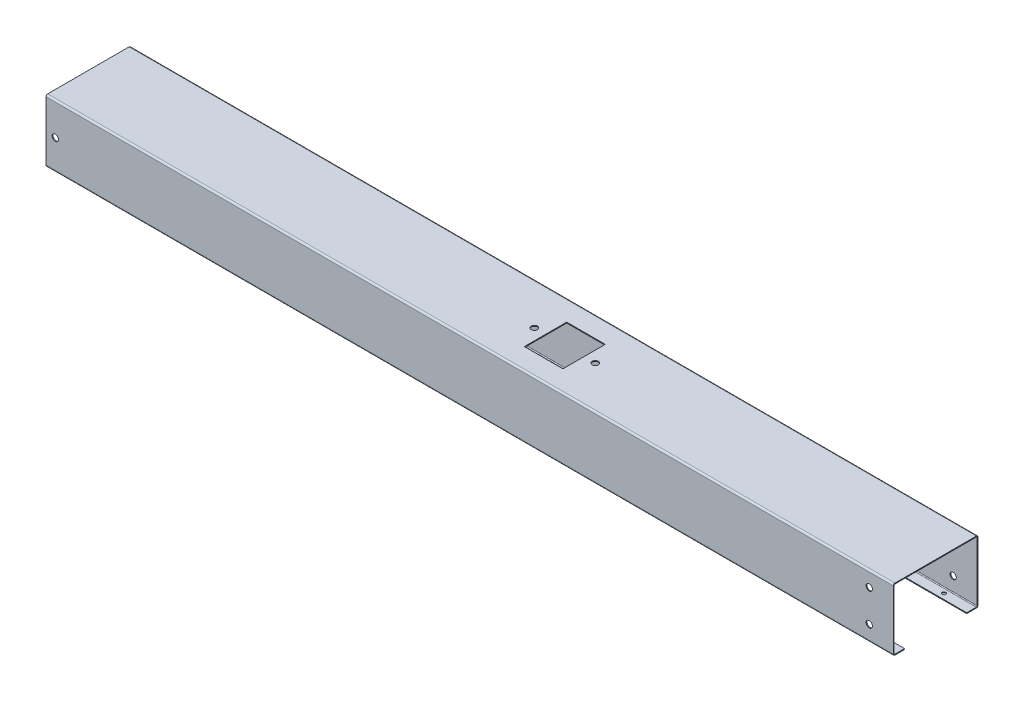
SolidWorks part; units mm, degrees
note: The reader was unsure of these and kept them because the rebuilt part matched: thickness of "Base-Flange1", "Edge-Flange1", "Edge-Flange2", "Sheet-Metal1", "Sheet-Metal2", "Sheet-Metal3", "Sheet-Metal5", "Sheet-Metal15", "Sheet-Metal16", "Sheet-Metal17", "Sheet-Metal18", "Sheet-Metal19"; flange length of "Edge-Flange1", "Edge-Flange2".
ref_plane "Front Plane" through (0, 0, 0) normal (0, 0, 1) x (1, 0, 0)
ref_plane "Top Plane" through (0, 0, 0) normal (0, 1, 0) x (1, 0, 0)
ref_plane "Right Plane" through (0, 0, 0) normal (1, 0, 0) x (0, 0, -1)
sketch "Sketch1" plane through (0, 0, 0) normal (0, 1, 0) x (1, 0, 0)
  line L1 (-381, -38.1) -> (381, -38.1)
  line L2 (-381, -38.1) -> (-381, 38.1)
  line L3 (-381, 38.1) -> (381, 38.1)
  line L4 (381, -38.1) -> (381, 38.1)
  line L5 (-381, -38.1) -> (381, 38.1) construction
  line L6 (-381, 38.1) -> (381, -38.1) construction
  point P0 (0, 0)
  dimension "D1" = 762
  dimension "D2" = 76.2
base flange "Base-Flange1" sketch "Sketch1" thickness 0.7595 reverse thickness direction no parameters "D1"=0.7366
sketch "Sketch6" plane through (0, 0, 0) normal (0, 1, 0) x (1, 0, 0)
  line L0 (53.7835, 19.05) -> (64.8335, 19.05)
  line L1 (30.1625, -19.05) -> (53.7835, -19.05)
  line L2 (30.1625, -19.05) -> (30.1625, 19.05)
  line L3 (30.1625, 19.05) -> (53.7835, 19.05)
  line L4 (64.8335, -19.05) -> (64.8335, 19.05)
  line L5 (30.1625, -19.05) -> (64.8335, 19.05) construction
  line L6 (30.1625, 19.05) -> (64.8335, -19.05) construction
  line L11 (-381, -38.1) -> (381, -38.1) construction
  line L12 (-381, 38.1) -> (-381, -38.1) construction
  line L13 (53.7835, -19.05) -> (64.8335, -19.05)
  point P0 (47.498, 0)
  point P12 (30.1625, 0)
  point P16 (64.8335, 0)
  dimension "D1" = 34.671
  dimension "D2" = 38.1
  dimension "D3" = 38.1
  dimension "D4" = 428.498
extrude "Cut-Extrude1" cut sketch "Sketch6" against normal blind 10 normal cut yes
sketch "Sketch7" plane through (0, 0, 0) normal (0, 1, 0) x (1, 0, 0)
  line L0 (30.1625, 19.05) -> (30.1625, -19.05) construction
  line L1 (64.8335, -19.05) -> (64.8335, 19.05) construction
  circle A0 centre (20.0625, 0) radius 2.8194
  circle A1 centre (74.9335, 0) radius 2.8194
  dimension "D1" = 5.6388
  dimension "D2" = 10.1
  dimension "D4" = 5.6388
  dimension "D3" = 10.1
extrude "Cut-Extrude2" cut sketch "Sketch7" against normal blind 10 normal cut yes
edge flange "Edge-Flange1" sketch "Sketch37" flange profiles "Sketch37", "Sketch39" flange angle 90 flange length 55.372 flange position material inside bend radius 0.7366 thickness 0.7595 relief rectangular parameters "D6"=10, "D8"=0.254
sketch "Sketch37" plane through (0, -0.7595, -38.1) normal (0, 0, -1) x (1, 0, 0)
  line L0 (381, 0) -> (-381, 0) construction
  line L1 (381, 0) -> (-381, 0)
  line L2 (-381, 0) -> (-381, 54.6125)
  line L3 (-381, 54.6125) -> (381, 54.6125)
  line L4 (381, 54.6125) -> (381, 0)
sketch "Sketch39" plane through (0, -0.7595, 38.1) normal (0, 0, 1) x (-1, 0, 0)
  line L0 (381, 0) -> (-381, 0) construction
  line L1 (381, 0) -> (-381, 0)
  line L2 (-381, 0) -> (-381, 54.6125)
  line L3 (-381, 54.6125) -> (381, 54.6125)
  line L4 (381, 54.6125) -> (381, 0)
bend "EdgeBend8" bend radius 0.7366 bend angle 90 parameters "D5"=4
bend "EdgeBend9" bend radius 0.7366 bend angle 90 parameters "D5"=5
sketch "Sketch41" plane through (0, 0, -38.1) normal (0, 0, -1) x (-1, 0, 0)
  line L0 (365.66, -13.4595) -> (352.96, -13.4595) construction
  line L1 (365.66, -16.825) -> (352.96, -16.825)
  line L2 (365.66, -10.094) -> (352.96, -10.094)
  line L3 (381, -55.372) -> (381, -1.4961) construction
  line L6 (-353.06, -13.448) -> (-365.76, -13.448) construction
  line L7 (-353.06, -16.8135) -> (-365.76, -16.8135)
  line L10 (-353.06, -10.0825) -> (-365.76, -10.0825)
  line L11 (-381, 0) -> (-381, -1.4961) construction
  line L12 (-381, -1.4961) -> (-381, -55.372) construction
  arc A0 (365.66, -16.825) -> (365.66, -10.094) centre (365.66, -13.4595) ccw
  arc A1 (352.96, -10.094) -> (352.96, -16.825) centre (352.96, -13.4595) ccw
  arc A4 (-353.06, -16.8135) -> (-353.06, -10.0825) centre (-353.06, -13.448) ccw
  arc A5 (-365.76, -10.0825) -> (-365.76, -16.8135) centre (-365.76, -13.448) ccw
  point P2 (359.31, -13.4595)
  point P11 (-359.41, -13.448)
  point P21 (-381, -0.748)
  dimension "D1" = 6.731
  dimension "D4" = 12.7
  dimension "D8" = 6.731
  dimension "D2" = 21.69
  dimension "D3" = 12.7
  dimension "D5" = 12.7
  dimension "D6" = 21.59
  dimension "D7" = 12.7
extrude "Cut-Extrude3" [suppressed] cut sketch "Sketch41" against normal through all both and the other way through all
sketch "Sketch42" plane through (0, 0, -38.1) normal (0, 0, -1) x (-1, 0, 0)
  line L0 (-381, -55.372) -> (381, -55.372) construction
  line L1 (-381, -1.4961) -> (-381, -55.372) construction
  circle A0 centre (-359.41, -13.4595) radius 2.8194
  circle A1 centre (-359.41, -42.164) radius 2.8194
  dimension "D3" = 5.6388
  dimension "D1" = 12.7
  dimension "D2" = 21.59
  dimension "D4" = 21.59
  dimension "D5" = 13.208
extrude "Cut-Extrude4" cut sketch "Sketch42" against normal through all both and the other way through all normal cut yes
edge flange "Edge-Flange2" sketch "Sketch47" flange profiles "Sketch47", "Sketch48" flange angle 90 flange length 10.16 flange position material outside bend radius 0.7366 thickness 0.7595 relief rectangular parameters "D6"=10, "D8"=0.254
sketch "Sketch47" plane through (0, -55.372, -37.3405) normal (0, 1, 0) x (-1, 0, 0)
  line L2 (-381, 0) -> (-381, 9.4005)
  line L3 (-381, 9.4005) -> (381, 9.4005)
  line L4 (381, 9.4005) -> (381, 0)
  line L5 (381, 0) -> (-381, 0) construction
  line L6 (381, 0) -> (-381, 0)
sketch "Sketch48" plane through (0, -55.372, 37.3405) normal (0, 1, 0) x (1, 0, 0)
  line L0 (381, 0) -> (-381, 0) construction
  line L1 (381, 0) -> (-381, 0)
  line L2 (381, 0) -> (381, 9.4005)
  line L3 (381, 9.4005) -> (-381, 9.4005)
  line L4 (-381, 9.4005) -> (-381, 0)
bend "EdgeBend10" bend radius 0.7366 bend angle 90 parameters "D5"=6
bend "EdgeBend11" bend radius 0.7366 bend angle 90 parameters "D5"=7
sketch "Sketch49" plane through (0, -56.1315, 0) normal (0, -1, 0) x (1, 0, 0)
  line L0 (-381, 36.6039) -> (381, 36.6039) construction
  line L1 (381, 36.6039) -> (381, 27.94) construction
  circle A0 centre (254, -32.7939) radius 1.651
  circle A1 centre (254, 32.7939) radius 1.651
  circle A2 centre (0, 32.7939) radius 1.651
  circle A3 centre (0, -32.7939) radius 1.651
  circle A4 centre (-304.8, -32.7939) radius 1.651
  circle A5 centre (-304.8, 32.7939) radius 1.651
  circle A6 centre (-355.6, 32.7939) radius 1.651
  circle A7 centre (-355.6, -32.7939) radius 1.651
  circle A8 centre (355.6, -32.7939) radius 1.651
  circle A9 centre (355.6, 32.7939) radius 1.651
  circle A10 centre (152.4, 32.7939) radius 1.651
  circle A11 centre (152.4, -32.7939) radius 1.651
  circle A12 centre (-152.4, 32.7939) radius 1.651
  circle A13 centre (-152.4, -32.7939) radius 1.651
  dimension "D1" = 3.302
  dimension "D2" = 3.81
  dimension "D3" = 3.81
  dimension "D4" = 127
  dimension "D5" = 254
  dimension "D6" = 304.8
  dimension "D7" = 50.8
  dimension "D8" = 152.4
  dimension "D9" = 101.6
  dimension "D10" = 101.6
extrude "Cut-Extrude5" cut sketch "Sketch49" against normal up to next normal cut yes
sketch "Sketch50" plane through (0, 0, 38.1) normal (0, 0, 1) x (1, 0, 0)
  line L0 (-381, -1.4961) -> (-381, -54.6354) construction
  circle A0 centre (-372.618, -29.21) radius 2.8194
  dimension "D1" = 5.6388
  dimension "D2" = 29.21
  dimension "D3" = 8.382
extrude "Cut-Extrude6" cut sketch "Sketch50" against normal through all both and the other way through all normal cut yes
sketch "Bend-Lines1" [suppressed] plane through (0, 0, 0) normal (0, 1, 0) x (1, 0, 0)
sketch "Bounding-Box1" [suppressed] plane through (0, 0, 0) normal (0, 1, 0) x (1, 0, 0)
sheet metal parameters "Sheet-Metal1" thickness 0.7595 parameters "D1"=0.7366
flat pattern "Flat-Pattern1" [suppressed]
sketch "Bend-Lines2" plane through (0, 0, 0) normal (0, 1, 0) x (1, 0, 0)
sketch3d "Bounding-Box2" [suppressed]
  line L0 (50.8, 38.1, 0) -> (-50.8, 38.1, 0) construction
  line L1 (50.8, -38.1, 0) -> (-50.8, -38.1, 0) construction
  line L2 (50.8, 38.1, 0) -> (50.8, -38.1, 0) construction
  line L3 (-50.8, 38.1, 0) -> (-50.8, -38.1, 0) construction
sheet metal parameters "Sheet-Metal2" thickness 0.7595 parameters "D1"=0.7366, "D7"=1.7366
flat pattern "Flat-Pattern1"
sketch "Bend-Lines2" plane through (0, 0, 0) normal (0, 1, 0) x (1, 0, 0)
sketch3d "Bounding-Box2" [suppressed]
  line L0 (571.5, 38.1, 0) -> (-571.5, 38.1, 0) construction
  line L1 (571.5, -38.1, 0) -> (-571.5, -38.1, 0) construction
  line L2 (571.5, 38.1, 0) -> (571.5, -38.1, 0) construction
  line L3 (-571.5, 38.1, 0) -> (-571.5, -38.1, 0) construction
sheet metal parameters "Sheet-Metal3" thickness 0.7595 parameters "D1"=0.7366, "D7"=1.7366
flat pattern "Flat-Pattern1"
sketch "Bend-Lines2" plane through (0, 0, 0) normal (0, 1, 0) x (1, 0, 0)
sketch3d "Bounding-Box2" [suppressed]
  line L0 (571.5, 31.75, 0) -> (-571.5, 31.75, 0) construction
  line L1 (571.5, -31.75, 0) -> (-571.5, -31.75, 0) construction
  line L2 (571.5, 31.75, 0) -> (571.5, -31.75, 0) construction
  line L3 (-571.5, 31.75, 0) -> (-571.5, -31.75, 0) construction
sheet metal parameters "Sheet-Metal5" thickness 0.7595 parameters "D1"=0.7366, "D7"=1.7366
flat pattern "Flat-Pattern1"
sketch "Bend-Lines2" plane through (0, 0, 0) normal (0, 1, 0) x (1, 0, 0)
  line L2 (-381, -37.4807) -> (381, -37.4807) construction
  line L3 (381, 37.4807) -> (-381, 37.4807) construction
  line L5 (-381, -37.4807) -> (381, -37.4807) construction
  line L6 (381, 37.4807) -> (-381, 37.4807) construction
sketch3d "Bounding-Box2" [suppressed]
  line L0 (381, 94.0114, 0) -> (-381, 94.0114, 0) construction
  line L1 (381, -94.0114, 0) -> (-381, -94.0114, 0) construction
  line L2 (381, 94.0114, 0) -> (381, -94.0114, 0) construction
  line L3 (-381, 94.0114, 0) -> (-381, -94.0114, 0) construction
bend of the flat pattern "Flatten-<EdgeBend8>1"
bend of the flat pattern "Flatten-<EdgeBend9>1"
sheet metal parameters "Sheet-Metal15" thickness 0.7595 parameters "D1"=0.7366, "D7"=1.7366
flat pattern "Flat-Pattern1"
sketch "Bend-Lines2" plane through (0, 0, 0) normal (0, 1, 0) x (1, 0, 0)
  line L2 (-381, -37.4807) -> (381, -37.4807) construction
  line L3 (381, 37.4807) -> (-381, 37.4807) construction
  line L5 (-381, -37.4807) -> (381, -37.4807) construction
  line L6 (381, 37.4807) -> (-381, 37.4807) construction
sketch3d "Bounding-Box2" [suppressed]
  line L0 (381, 94.0114, 0) -> (-381, 94.0114, 0) construction
  line L1 (381, -94.0114, 0) -> (-381, -94.0114, 0) construction
  line L2 (381, 94.0114, 0) -> (381, -94.0114, 0) construction
  line L3 (-381, 94.0114, 0) -> (-381, -94.0114, 0) construction
bend of the flat pattern "Flatten-<EdgeBend8>1"
bend of the flat pattern "Flatten-<EdgeBend9>1"
sheet metal parameters "Sheet-Metal16" thickness 0.7595 parameters "D1"=0.7366, "D7"=1.7366
flat pattern "Flat-Pattern1"
sketch "Bend-Lines2" plane through (0, 0, 0) normal (0, 1, 0) x (1, 0, 0)
  line L2 (-381, -37.4807) -> (381, -37.4807) construction
  line L3 (381, 37.4807) -> (-381, 37.4807) construction
  line L5 (-381, -37.4807) -> (381, -37.4807) construction
  line L6 (381, 37.4807) -> (-381, 37.4807) construction
sketch3d "Bounding-Box2" [suppressed]
  line L0 (381, 93.5034, 0) -> (-381, 93.5034, 0) construction
  line L1 (381, -93.5034, 0) -> (-381, -93.5034, 0) construction
  line L2 (381, 93.5034, 0) -> (381, -93.5034, 0) construction
  line L3 (-381, 93.5034, 0) -> (-381, -93.5034, 0) construction
bend of the flat pattern "Flatten-<EdgeBend8>1"
bend of the flat pattern "Flatten-<EdgeBend9>1"
sheet metal parameters "Sheet-Metal17" thickness 0.7595 parameters "D1"=0.7366, "D7"=1.7366
flat pattern "Flat-Pattern1"
sketch "Bend-Lines2" plane through (0, 0, 0) normal (0, 1, 0) x (1, 0, 0)
  line L0 (-381, -93.6436) -> (381, -93.6436) construction
  line L1 (381, 93.6436) -> (-381, 93.6436) construction
  line L2 (-381, -37.4807) -> (381, -37.4807) construction
  line L3 (381, 37.4807) -> (-381, 37.4807) construction
  line L4 (-381, -93.6436) -> (381, -93.6436) construction
  line L5 (-381, -37.4807) -> (381, -37.4807) construction
  line L6 (381, 37.4807) -> (-381, 37.4807) construction
  line L7 (381, 93.6436) -> (-381, 93.6436) construction
sketch3d "Bounding-Box2" [suppressed]
  line L0 (381, 103.1843, 0) -> (-381, 103.1843, 0) construction
  line L1 (381, -103.1843, 0) -> (-381, -103.1843, 0) construction
  line L2 (381, 103.1843, 0) -> (381, -103.1843, 0) construction
  line L3 (-381, 103.1843, 0) -> (-381, -103.1843, 0) construction
bend of the flat pattern "Flatten-<EdgeBend8>1"
bend of the flat pattern "Flatten-<EdgeBend9>1"
bend of the flat pattern "Flatten-<EdgeBend10>1"
bend of the flat pattern "Flatten-<EdgeBend11>1"
sheet metal parameters "Sheet-Metal18" thickness 0.7595 parameters "D1"=0.7366, "D7"=1.7366
flat pattern "Flat-Pattern1"
sketch "Bend-Lines2" plane through (0, 0, 0) normal (0, 1, 0) x (1, 0, 0)
  line L0 (-381, -93.6436) -> (381, -93.6436) construction
  line L1 (381, 93.6436) -> (-381, 93.6436) construction
  line L2 (-381, -37.4807) -> (381, -37.4807) construction
  line L3 (381, 37.4807) -> (-381, 37.4807) construction
  line L4 (-381, -93.6436) -> (381, -93.6436) construction
  line L5 (-381, -37.4807) -> (381, -37.4807) construction
  line L6 (381, 37.4807) -> (-381, 37.4807) construction
  line L7 (381, 93.6436) -> (-381, 93.6436) construction
sketch3d "Bounding-Box2" [suppressed]
  line L0 (381, 103.1843, 0) -> (-381, 103.1843, 0) construction
  line L1 (381, -103.1843, 0) -> (-381, -103.1843, 0) construction
  line L2 (381, 103.1843, 0) -> (381, -103.1843, 0) construction
  line L3 (-381, 103.1843, 0) -> (-381, -103.1843, 0) construction
bend of the flat pattern "Flatten-<EdgeBend8>1"
bend of the flat pattern "Flatten-<EdgeBend9>1"
bend of the flat pattern "Flatten-<EdgeBend10>1"
bend of the flat pattern "Flatten-<EdgeBend11>1"
sheet metal parameters "Sheet-Metal19" thickness 0.7595 parameters "D1"=0.7366, "D7"=1.7366
flat pattern "Flat-Pattern1"
sketch "Bend-Lines2" plane through (0, 0, 0) normal (0, 1, 0) x (1, 0, 0)
  line L0 (-381, -92.3736) -> (381, -92.3736) construction
  line L1 (381, 92.3736) -> (-381, 92.3736) construction
  line L2 (-381, -37.4807) -> (381, -37.4807) construction
  line L3 (381, 37.4807) -> (-381, 37.4807) construction
  line L4 (-381, -92.3736) -> (381, -92.3736) construction
  line L5 (-381, -37.4807) -> (381, -37.4807) construction
  line L6 (381, 37.4807) -> (-381, 37.4807) construction
  line L7 (381, 92.3736) -> (-381, 92.3736) construction
sketch3d "Bounding-Box2" [suppressed]
  line L0 (381, 101.9143, 0) -> (-381, 101.9143, 0) construction
  line L1 (381, -101.9143, 0) -> (-381, -101.9143, 0) construction
  line L2 (381, 101.9143, 0) -> (381, -101.9143, 0) construction
  line L3 (-381, 101.9143, 0) -> (-381, -101.9143, 0) construction
bend of the flat pattern "Flatten-<EdgeBend8>1"
bend of the flat pattern "Flatten-<EdgeBend9>1"
bend of the flat pattern "Flatten-<EdgeBend10>1"
bend of the flat pattern "Flatten-<EdgeBend11>1"
